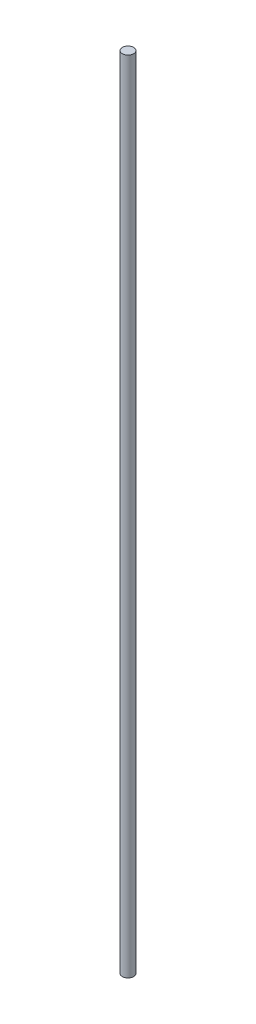
SolidWorks part; units mm, degrees
ref_plane "Front Plane" through (0, 0, 0) normal (0, 0, 1) x (1, 0, 0)
ref_plane "Top Plane" through (0, 0, 0) normal (0, 1, 0) x (1, 0, 0)
ref_plane "Right Plane" through (0, 0, 0) normal (1, 0, 0) x (0, 0, -1)
sketch "Sketch1" plane through (0, 0, 0) normal (0, 1, 0) x (1, 0, 0)
  circle A0 centre (0, 0) radius 1.4224
  dimension "D1" = 2.8448
extrude "Boss-Extrude1" add sketch "Sketch1" along normal blind 203.2
